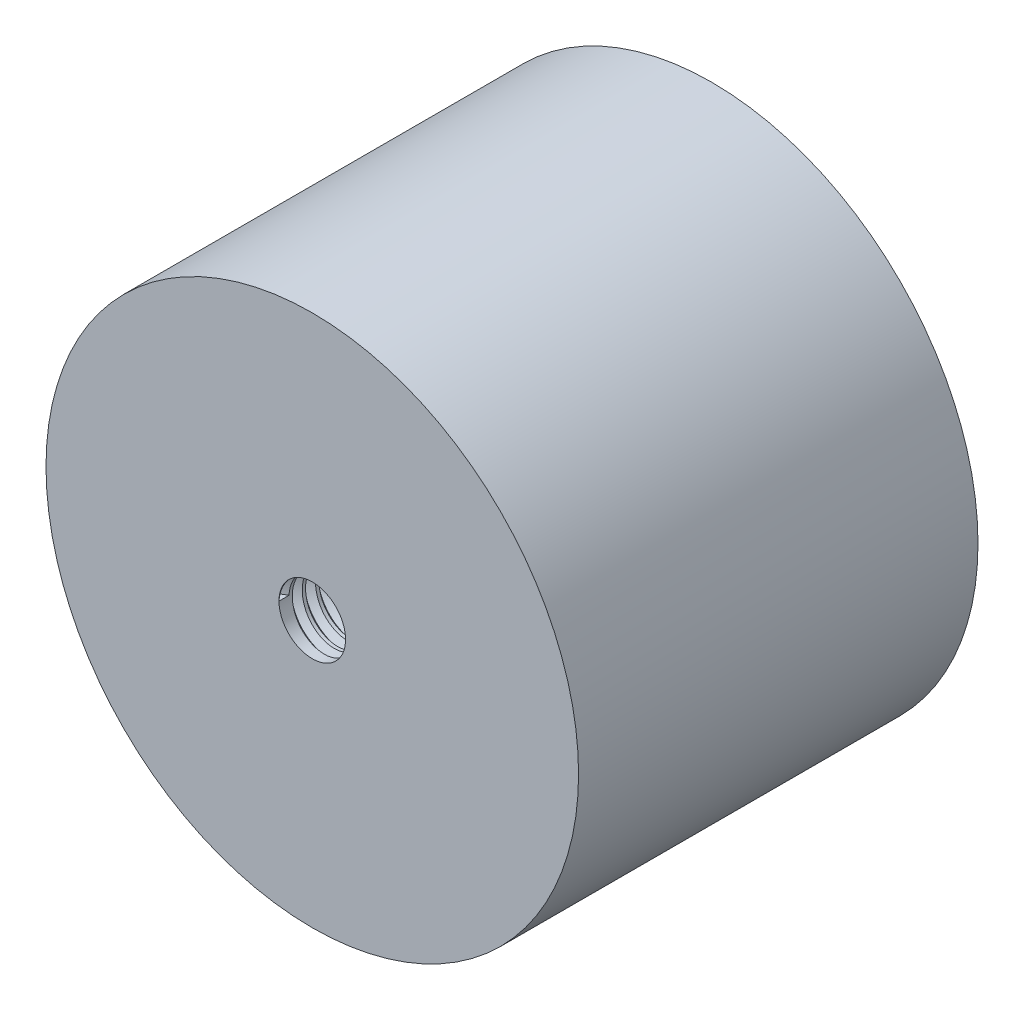
SolidWorks part; units mm, degrees
material "Stainless Steel (ferritic)"
ref_plane "Front Plane" through (0, 0, 0) normal (0, 0, 1) x (1, 0, 0)
ref_plane "Top Plane" through (0, 0, 0) normal (0, 1, 0) x (1, 0, 0)
ref_plane "Right Plane" through (0, 0, 0) normal (1, 0, 0) x (0, 0, -1)
sketch "Sketch1" plane through (0, 0, 0) normal (0, 0, 1) x (1, 0, 0)
  circle A0 centre (0, 0) radius 10
  dimension "20" = 20
extrude "Boss-Extrude1" add sketch "Sketch1" along normal blind 15
hole_wizard "Tap Drill for M3 Tap1" positions "Sketch6" profile "Sketch7" hole size "M3" standard "ISO"
sketch "Sketch6" plane through (0, 0, 15) normal (0, 0, 1) x (1, 0, 0)
  point P0 (0, 0)
sketch "Sketch7" plane through (0, 0, 15) normal (1, 0, 0) x (0, -1, 0)
  line L0 (0, 0) -> (0, 10.7511)
  line L1 (0, 10.7511) -> (1.25, 10)
  line L2 (1.25, 10) -> (1.25, 0)
  line L5 (1.25, 0) -> (0, 0)
  line L10 (0, 10.7511) -> (-1.25, 10) construction
  line L11 (0, -6.35) -> (0, 107.95) construction
  dimension "Hole Dia." = 2.5
  dimension "Hole Depth" = 10
  dimension "Drill Angle" = 118
thread "Thread1" pitch 0.5 method cut profile "Thread Profile1" start angle 0, offset 0, length 10, pitch 0.5, diameter 2.5
ref_plane "Plane1" through (-1.25, 0, 15) normal (0, -1, 0) x (-1, 0, 0)
sketch "Thread Profile1" plane through (-1.25, 0, 15) normal (0, -1, 0) x (-1, 0, 0)
  line L0 (0, 0) -> (0, 0.5) construction
  line L1 (0, 0) -> (0.2706, 0.1562)
  line L2 (0.2706, 0.1562) -> (0.2706, 0.2187)
  line L3 (0.2706, 0.2187) -> (0, 0.375)
  line L4 (0.2706, 0.1875) -> (0, 0.1875) construction
  line L11 (0, 0) -> (0, 0.375)
  point P2 (0, 0)
  dimension "Pitch" = 0.5
  dimension "Profile_Angle" = 60
  dimension "Profile_Land" = 0.0625
  dimension "Profile_Height" = 0.2706
